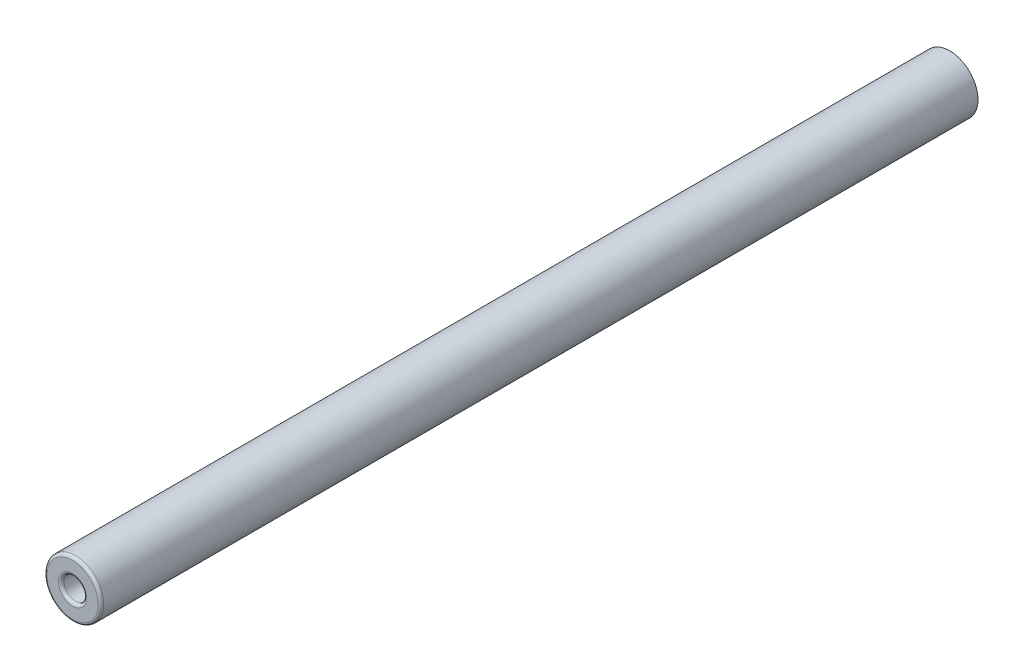
SolidWorks part; units mm, degrees
material "Acero aleado"
ref_plane "Alzado" through (0, 0, 0) normal (0, 0, 1) x (1, 0, 0)
ref_plane "Planta" through (0, 0, 0) normal (0, 1, 0) x (1, 0, 0)
ref_plane "Vista lateral" through (0, 0, 0) normal (1, 0, 0) x (0, 0, -1)
sketch "Croquis1" plane through (0, 0, 0) normal (0, 0, 1) x (1, 0, 0)
  circle A0 centre (0, 0) radius 2.5
  dimension "D1" = 5
extrude "Saliente-Extruir1" add sketch "Croquis1" along normal blind 77.5
sketch "Croquis2" plane through (0, 0, 77.5) normal (0, 0, 1) x (1, 0, 0)
  circle A0 centre (0, 0) radius 1
  dimension "D1" = 2
extrude "Cortar-Extruir1" cut sketch "Croquis2" against normal blind 10
fillet "Redondeo1" radius 0.25 2 edges at (2.5, 0, 77.5) (1, 0, 77.5)
